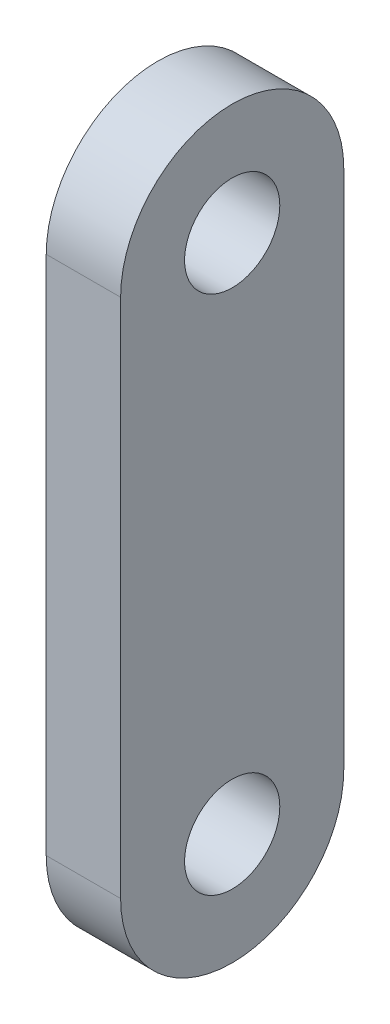
SolidWorks part; units mm, degrees
ref_plane "Front Plane" through (0, 0, 0) normal (0, 0, 1) x (1, 0, 0)
ref_plane "Top Plane" through (0, 0, 0) normal (0, 1, 0) x (1, 0, 0)
ref_plane "Right Plane" through (0, 0, 0) normal (1, 0, 0) x (0, 0, -1)
sketch "Sketch1" plane through (0, 0, 0) normal (1, 0, 0) x (0, 0, -1)
  line L0 (0, 0) -> (0, 22.225) construction
  line L1 (-4.7625, 0) -> (-4.7625, 22.225)
  line L2 (4.7625, 0) -> (4.7625, 22.225)
  arc A0 (-4.7625, 0) -> (4.7625, 0) centre (0, 0) ccw
  arc A1 (4.7625, 22.225) -> (-4.7625, 22.225) centre (0, 22.225) ccw
  circle A2 centre (0, 22.225) radius 2.032
  circle A3 centre (0, 0) radius 2.032
  point P3 (0, 11.1125)
  dimension "D2" = 9.525
  dimension "D3" = 4.064
  dimension "D1" = 22.225
extrude "Boss-Extrude1" add sketch "Sketch1" along normal blind 3.175
